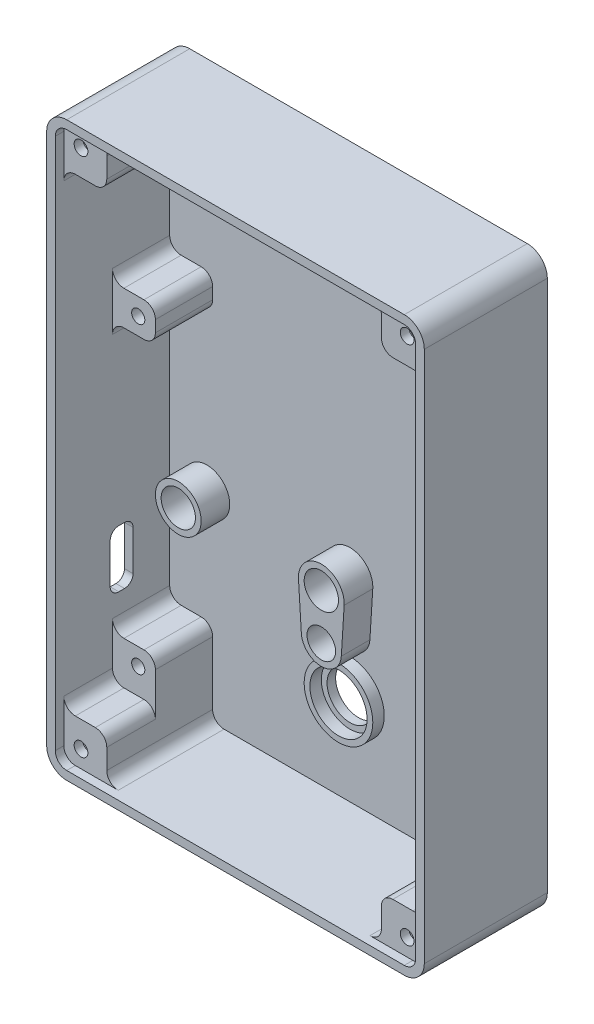
SolidWorks part; units mm, degrees
material "ABS"
ref_plane "Спереди" through (0, 0, 0) normal (0, 0, 1) x (1, 0, 0)
ref_plane "Сверху" through (0, 0, 0) normal (0, 1, 0) x (1, 0, 0)
ref_plane "Справа" through (0, 0, 0) normal (1, 0, 0) x (0, 0, -1)
sketch "Эскиз1" plane through (0, 0, 0) normal (0, 0, 1) x (1, 0, 0)
  line L1 (-33, -50) -> (33, -50)
  line L2 (-33, -50) -> (-33, 50)
  line L3 (-33, 50) -> (33, 50)
  line L4 (33, -50) -> (33, 50)
  line L5 (-33, -50) -> (33, 50) construction
  line L6 (-33, 50) -> (33, -50) construction
  line L7 (-31.5, -48.5) -> (31.5, -48.5)
  line L8 (-31.5, -48.5) -> (-31.5, 48.5)
  line L9 (-31.5, 48.5) -> (31.5, 48.5)
  line L10 (31.5, -48.5) -> (31.5, 48.5)
  line L11 (-31.5, -48.5) -> (31.5, 48.5) construction
  line L12 (-31.5, 48.5) -> (31.5, -48.5) construction
  point P0 (0, 0)
  point P6 (0, 0)
  dimension "D1" = 66
  dimension "D2" = 100
  dimension "D3" = 1.5
  dimension "D4" = 1.5
extrude "Бобышка-Вытянуть1" add sketch "Эскиз1" along normal blind 20
sketch "Эскиз3" plane through (0, 0, 0) normal (0, 0, -1) x (-1, 0, 0)
  line L1 (-33, 50) -> (33, 50)
  line L2 (-33, 50) -> (-33, -50)
  line L3 (-33, -50) -> (33, -50)
  line L4 (33, 50) -> (33, -50)
extrude "Бобышка-Вытянуть2" add sketch "Эскиз3" along normal blind 1.5
sketch "Эскиз4" plane through (0, 0, 0) normal (0, 0, 1) x (1, 0, 0)
  line L0 (-31.5, 48.5) -> (-31.5, -48.5) construction
  line L1 (-31.5, 19.5) -> (-24, 19.5)
  line L2 (-31.5, 19.5) -> (-31.5, 13.5)
  line L3 (-31.5, 13.5) -> (-24, 13.5)
  line L4 (-24, 19.5) -> (-24, 13.5)
  line L5 (31.5, -48.5) -> (31.5, 48.5) construction
  line L6 (31.5, 19.5) -> (24, 19.5)
  line L7 (31.5, 19.5) -> (31.5, 13.5)
  line L8 (31.5, 13.5) -> (24, 13.5)
  line L9 (24, 19.5) -> (24, 13.5)
  line L10 (-31.5, -48.5) -> (31.5, -48.5) construction
  line L11 (-31.5, -41) -> (-24, -41)
  line L12 (-31.5, -41) -> (-31.5, -33.5)
  line L13 (-31.5, -33.5) -> (-24, -33.5)
  line L14 (-24, -41) -> (-24, -33.5)
  line L15 (31.5, -41) -> (24, -41)
  line L16 (31.5, -41) -> (31.5, -33.5)
  line L17 (31.5, -33.5) -> (24, -33.5)
  line L18 (24, -41) -> (24, -33.5)
  line L19 (31.5, -48.5) -> (31.5, 48.5) construction
  dimension "D1" = 7.5
  dimension "D2" = 7.5
  dimension "D3" = 6
  dimension "D4" = 47
  dimension "D5" = 7.5
extrude "Бобышка-Вытянуть3" add sketch "Эскиз4" along normal blind 10
sketch "Эскиз5" plane through (0, 0, 10) normal (0, 0, 1) x (1, 0, 0)
  line L0 (-24, 13.5) -> (-24, 19.5) construction
  line L1 (24, 19.5) -> (24, 13.5) construction
  line L2 (-31.5, 13.5) -> (-24, 13.5) construction
  line L3 (-24, -33.5) -> (-31.5, -33.5) construction
  point P0 (-27, 16.5)
  point P1 (27, 16.5)
  point P2 (27, -36.5)
  point P3 (-27, -36.5)
  dimension "D1" = 3
  dimension "D2" = 3
  dimension "D3" = 3
  dimension "D4" = 3
hole_wizard "Сверло под метчик  спиральное M2.21" positions "Эскиз6" profile "Эскиз7" hole size "M2.2x0.45" standard "DIN"
sketch "Эскиз6" plane through (0, 0, 10) normal (0, 0, 1) x (1, 0, 0)
  point P0 (-27, 16.5)
  point P3 (27, 16.5)
  point P6 (27, -36.5)
  point P9 (-27, -36.5)
sketch "Эскиз7" plane through (-27, 16.5, 10) normal (1, 0, 0) x (0, -1, 0)
  line L0 (0, 0) -> (0, 4.691)
  line L1 (0, 4.691) -> (1.15, 4)
  line L2 (1.15, 4) -> (1.15, 0)
  line L5 (1.15, 0) -> (0, 0)
  line L10 (0, 4.691) -> (-1.15, 4) construction
  line L11 (0, -6.35) -> (0, 107.95) construction
  dimension "Диаметр отверстия" = 2.3
  dimension "Глубина отверстия" = 4
  dimension "Угол заточки сверла" = 118
sketch "Эскиз8" plane through (0, 0, 0) normal (0, 0, 1) x (1, 0, 0)
  line L0 (-24, -41) -> (-24, -33.5) construction
  line L1 (-31.5, 48.5) -> (-24, 48.5)
  line L2 (-31.5, 48.5) -> (-31.5, 41)
  line L3 (-31.5, 41) -> (-24, 41)
  line L4 (-24, 48.5) -> (-24, 41)
  line L5 (31.5, 48.5) -> (24, 48.5)
  line L6 (31.5, 48.5) -> (31.5, 41)
  line L7 (31.5, 41) -> (24, 41)
  line L8 (24, 48.5) -> (24, 41)
  line L9 (31.5, -48.5) -> (24, -48.5)
  line L10 (31.5, -48.5) -> (31.5, -41)
  line L11 (31.5, -41) -> (24, -41)
  line L12 (24, -48.5) -> (24, -41)
  line L13 (-31.5, -48.5) -> (-24, -48.5)
  line L14 (-31.5, -48.5) -> (-31.5, -41)
  line L15 (-31.5, -41) -> (-24, -41)
  line L16 (-24, -48.5) -> (-24, -41)
  line L18 (24, -33.5) -> (24, -41) construction
  line L19 (-24, 19.5) -> (-31.5, 19.5) construction
  line L21 (-31.5, -41) -> (-24, -41) construction
extrude "Бобышка-Вытянуть4" add sketch "Эскиз8" along normal blind 18.5
fillet "Скругление1" radius 2 20 edges at (-31.5, -33.5, 5) (-24, -33.5, 5) (-24, -48.5, 9.25) (24, -48.5, 9.25) (24, -33.5, 5) (31.5, -33.5, 5) (31.5, 13.5, 5) (24, 13.5, 5) (24, 19.5, 5) (31.5, 19.5, 5) (-31.5, 13.5, 5) (-24, 13.5, 5) (-24, 19.5, 5) (-31.5, 19.5, 5) (-31.5, 41, 9.25) (-24, 41, 9.25) (-24, 48.5, 9.25) (31.5, 41, 9.25) (24, 48.5, 9.25) (24, 41, 9.25)
fillet "Скругление3" radius 2 8 edges at (-31.5, -48.5, 19.25) (-31.5, -41, 14.25) (-24, -41, 14.25) (31.5, -48.5, 19.25) (24, -41, 14.25) (31.5, -41, 14.25) (-31.5, 48.5, 19.25) (31.5, 48.5, 19.25)
fillet "Скругление4" radius 3.5 4 edges at (-33, -50, 9.25) (33, -50, 9.25) (33, 50, 9.25) (-33, 50, 9.25)
sketch "Эскиз9" plane through (0, 0, 0) normal (0, 0, 1) x (1, 0, 0)
  line L2 (26, -41) -> (29.5, -41) construction
  circle A0 centre (-25, -14) radius 3
  circle A1 centre (25, -14) radius 3
  circle A2 centre (0, -22) radius 2.5
  circle A3 centre (0, -14) radius 3
  circle A4 centre (0, -32.5) radius 4
  dimension "D1" = 6
  dimension "D6" = 8
  dimension "D8" = 5
  dimension "D2" = 8
  dimension "D3" = 10.5
  dimension "D4" = 25
  dimension "D5" = 25
  dimension "D7" = 8.5
extrude "Вырез-Вытянуть1" cut sketch "Эскиз9" against normal through all
sketch "Эскиз10" plane through (0, 0, 0) normal (0, 0, 1) x (1, 0, 0)
  line L0 (3.9922, -14.25) -> (3.4932, -22.2188)
  line L1 (-3.9922, -14.25) -> (-3.4932, -22.2188)
  circle A0 centre (-25, -14) radius 3
  circle A1 centre (0, -22) radius 2.5 construction
  circle A2 centre (0, -14) radius 3
  circle A3 centre (25, -14) radius 3
  circle A4 centre (0, -22) radius 2.5
  circle A5 centre (-25, -14) radius 3 construction
  circle A6 centre (0, -14) radius 4
  circle A7 centre (25, -14) radius 4
  circle A9 centre (-25, -14) radius 4
  arc A12 (-3.4932, -22.2188) -> (3.4932, -22.2188) centre (0, -22) ccw
  circle M1 centre (-25, -14) radius 3
  circle M2 centre (0, -14) radius 3
  circle M3 centre (0, -22) radius 2.5
  circle M4 centre (25, -14) radius 3
  dimension "D1" = 1
  dimension "D2" = 1
extrude "Бобышка-Вытянуть5" add sketch "Эскиз10" along normal blind 5 contours L1 A12 L0 A6 M3 | A6 M2 | A7 M4 | A9 M1 region at (3.605, -18.2258, 0) region at (0, -17.8869, 0) region at (21.1131, -14, 0) region at (-28.8869, -14, 0)
sketch "Эскиз11" plane through (0, 0, -1.5) normal (0, 0, -1) x (-1, 0, 0)
  line L0 (29.5, 50) -> (-29.5, 50) construction
  line L1 (33, -46.5) -> (33, 46.5) construction
  line L2 (-29.5, -50) -> (29.5, -50) construction
  line L3 (-33, 46.5) -> (-33, -46.5) construction
  circle A0 centre (-28.5, 45.5) radius 2.5
  circle A1 centre (28.5, 45.5) radius 2.5
  circle A2 centre (28.5, -45.5) radius 2.5
  circle A3 centre (-28.5, -45.5) radius 2.5
  dimension "D2" = 5
  dimension "D1" = 4.5
  dimension "D3" = 4.5
  dimension "D4" = 4.5
  dimension "D5" = 4.5
extrude "Вырез-Вытянуть2" cut sketch "Эскиз11" against normal blind 18.5
sketch "Эскиз12" plane through (0, 0, 17) normal (0, 0, -1) x (-1, 0, 0)
  point P0 (-28.5, 45.5)
  point P1 (28.5, 45.5)
  point P3 (28.5, -45.5)
  point P5 (-28.5, -45.5)
hole_wizard "Отверстие с зазором M21" positions "Эскиз13" profile "Эскиз14" hole size "M2" standard "DIN" end condition through all
sketch "Эскиз13" plane through (0, 0, 17) normal (0, 0, -1) x (-1, 0, 0)
  point P0 (-28.5, 45.5)
  point P3 (28.5, 45.5)
  point P6 (28.5, -45.5)
  point P9 (-28.5, -45.5)
sketch "Эскиз14" plane through (28.5, 45.5, 17) normal (1, 0, 0) x (0, 1, 0)
  line L0 (0, 0) -> (0, 3)
  line L1 (0, 3) -> (1.2, 3)
  line L2 (1.2, 3) -> (1.2, 0)
  line L5 (1.2, 0) -> (0, 0)
  line L11 (0, -6.35) -> (0, 107.95) construction
  dimension "Диаметр сквозного отверстия" = 2.4
  dimension "Глубина сквозного отверстия" = 3
sketch "Эскиз15" plane through (-31.5, 0, 0) normal (-1, 0, 0) x (0, 0, 1)
  line L1 (6.4, -28) -> (10.4, -28)
  line L2 (6.4, -28) -> (6.4, -18)
  line L3 (6.4, -18) -> (10.4, -18)
  line L4 (10.4, -28) -> (10.4, -18)
  line L5 (10, -39) -> (10, -31.5) construction
  dimension "D1" = 4
  dimension "D2" = 10
  dimension "D3" = 8.5
  dimension "D4" = 0.4
extrude "Вырез-Вытянуть3" cut sketch "Эскиз15" along normal up to surface (1.5 mm away) up to face at (-33, 0, 9.25)
fillet "Скругление5" radius 1.5 4 edges at (-32.25, -28, 10.4) (-32.25, -18, 10.4) (-32.25, -18, 6.4) (-32.25, -28, 6.4)
sketch "Эскиз16" plane through (0, 0, 0) normal (0, 0, 1) x (1, 0, 0)
  circle A0 centre (0, -32.5) radius 5
  circle A1 centre (0, -32.5) radius 6
  dimension "D1" = 1
  dimension "D2" = 10
extrude "Бобышка-Вытянуть6" add sketch "Эскиз16" along normal blind 2
